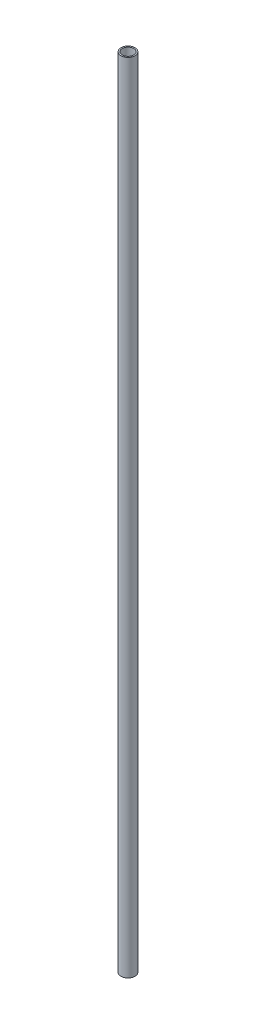
SolidWorks part; units mm, degrees
material "Hexcel AS4C (3000 Filaments)"
ref_plane "Front Plane" through (0, 0, 0) normal (0, 0, 1) x (1, 0, 0)
ref_plane "Top Plane" through (0, 0, 0) normal (0, 1, 0) x (1, 0, 0)
ref_plane "Right Plane" through (0, 0, 0) normal (1, 0, 0) x (0, 0, -1)
sketch "Sketch1" plane through (0, 0, 0) normal (0, 1, 0) x (1, 0, 0)
  circle A0 centre (0, 0) radius 4.825
  circle A1 centre (0, 0) radius 3.925
  dimension "D1" = 9.65
  dimension "D2" = 7.85
extrude "Boss-Extrude1" add sketch "Sketch1" along normal blind 550
